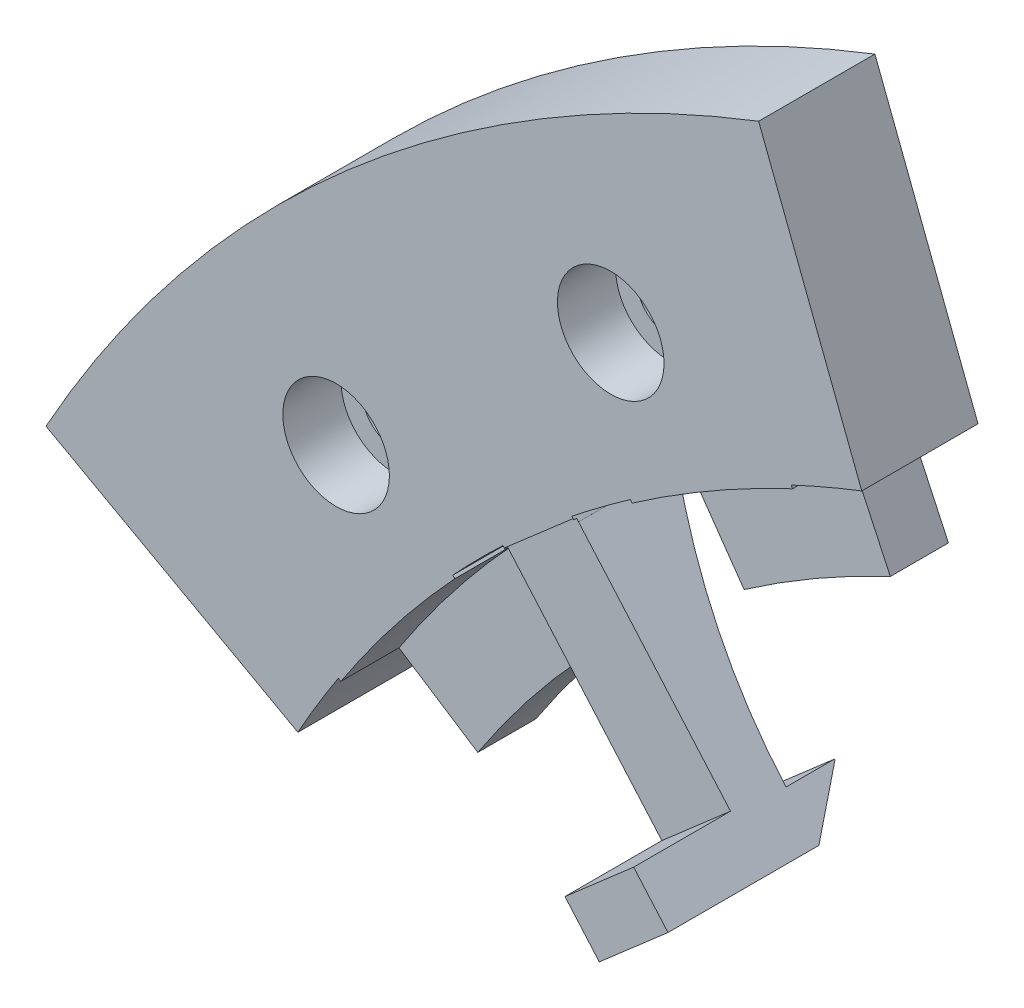
SolidWorks part; units mm, degrees
ref_plane "Front Plane" through (0, 0, 0) normal (1, 0, 0) x (0, 1, 0)
ref_plane "Top Plane" through (0, 0, 0) normal (0, 0, 1) x (0, 1, 0)
ref_plane "Right Plane" through (0, 0, 0) normal (0, 1, 0) x (-1, 0, 0)
sketch "Sketch1" plane through (0, 0, 0) normal (0, 0, 1) x (0, 1, 0)
  line L0 (0, 0) -> (50000, 0) construction
  line L1 (66.793, 25.6394) -> (52.7893, 20.2639)
  line L2 (52.7893, 20.2639) -> (0, 0) construction
  line L3 (34.5874, 62.6291) -> (27.3358, 49.4984)
  line L4 (27.3358, 49.4984) -> (0, 0) construction
  arc A0 (34.5874, 62.6291) -> (66.793, 25.6394) centre (0, 0) cw
  arc A1 (52.7893, 20.2639) -> (27.3358, 49.4984) centre (0, 0) ccw
  dimension "D1" = 71.545
  dimension "D3" = 40.09
  dimension "D4" = 15
  dimension "D2" = 21
extrude "Boss-Extrude1" add sketch "Sketch1" along normal blind 6
ref_axis "Axis1" through (0, 0, 0) along (0, 1, 0)
sketch "Sketch4" plane through (0, 0, 0) normal (0, 0, 1) x (0, 1, 0)
  line L0 (41.3645, 47.5844) -> (0, 0) construction
  line L1 (0, 0) -> (53.4694, 33.4114) construction
  line L2 (0, 0) -> (15.7813, 0) construction
  circle A0 centre (41.3645, 47.5844) radius 1.65
  circle A1 centre (53.4694, 33.4114) radius 1.65
  dimension "D1" = 3.3
  dimension "D2" = 63.05
  dimension "D3" = 32
  dimension "D4" = 49
extrude "Cut-Extrude1" cut sketch "Sketch4" along normal through all
ref_plane "Plane1" through (0, 0, 0) normal (-0.7542, -0.6567, 0) x (0, 0, 1)
ref_axis "Axis2" through (-37.1304, 42.6459, 0) along (0, 0, 1)
sketch "Sketch7" plane through (0, 0, 0) normal (-0.7542, -0.6567, 0) x (0, 0, 1)
  line L0 (6, 56.545) -> (6, 41.545) construction
  line L1 (6, 41.545) -> (3, 41.545)
  line L2 (0.5, 44.045) -> (0.5, 44.295)
  line L3 (0.5, 44.295) -> (3, 44.295)
  line L5 (0, 56.545) -> (6, 56.545) construction
  line L7 (0.5, 44.045) -> (3, 41.545)
  line L8 (6, 41.545) -> (11, 41.545)
  line L9 (11, 41.545) -> (11, 44.545)
  line L10 (11, 44.545) -> (6, 44.545)
  line L11 (6, 44.545) -> (6, 56.545)
  line L12 (0.5, 56.545) -> (6, 56.545)
  arc A1 (3, 44.295) -> (0.5, 56.545) centre (-28.2625, 44.295) ccw
  dimension "D4" = 45
  dimension "D1" = 15
  dimension "D2" = 3
  dimension "D3" = 5
  dimension "D5" = 3
  dimension "D6" = 5.5
  dimension "D7" = 3
  dimension "D8" = 0.25
extrude "Boss-Extrude2" add sketch "Sketch7" along normal blind 2.5 and the other way blind 2.5
fillet "Fillet1" radius 0.1 3 edges at (-29.0864, 33.407, 3) (-29.2505, 33.5956, 6)
sketch "Sketch8" plane through (0, 0, 0) normal (0, 0, 1) x (0, 1, 0)
  line L0 (0, 0) -> (30.7966, 47.4226) construction
  line L1 (38.5636, 41.3544) -> (0, 0) construction
  line L2 (0, 0) -> (46.319, 32.4329) construction
  line L3 (51.2472, 23.8969) -> (0, 0) construction
  line L4 (30.7966, 47.4226) -> (28.0734, 43.2293)
  line L5 (38.5636, 41.3544) -> (35.1536, 37.6976)
  line L6 (46.319, 32.4329) -> (42.2232, 29.565)
  line L7 (51.2472, 23.8969) -> (46.7156, 21.7839)
  line L8 (0, 0) -> (15.7813, 0) construction
  arc A0 (40.9626, 38.9795) -> (27.3358, 49.4984) centre (0, 0) ccw construction
  arc A1 (52.7893, 20.2639) -> (44.2458, 35.2086) centre (0, 0) ccw construction
  arc A2 (30.7966, 47.4226) -> (38.5636, 41.3544) centre (0, 0) cw
  arc A3 (46.319, 32.4329) -> (51.2472, 23.8969) centre (0, 0) cw
  arc A4 (28.0734, 43.2293) -> (35.1536, 37.6976) centre (0, 0) cw
  arc A5 (42.2232, 29.565) -> (46.7156, 21.7839) centre (0, 0) cw
  dimension "D1" = 51.545
  dimension "D2" = 56.545
  dimension "D3" = 25
  dimension "D4" = 10
  dimension "D5" = 12
  dimension "D6" = 10
extrude "Boss-Extrude3" add sketch "Sketch8" along normal blind 3 contours L4 A4 L5 A2 | L5 A4 L4 A2 | L7 A5 L6 A3 region at (-42.5643, 33.2549, 0)
sketch "Sketch9" plane through (0, 0, 6) normal (0, 0, 1) x (1, 0, 0)
  circle A0 centre (-47.5844, 41.3645) radius 2.75
  circle A1 centre (-33.4114, 53.4694) radius 2.75
  dimension "D1" = 5.5
extrude "Cut-Extrude2" cut sketch "Sketch9" against normal blind 3
sketch "Sketch10" plane through (0, 0, 0) normal (0, 0, 1) x (0, 1, 0)
  line L0 (38.5636, 41.3544) -> (35.1536, 37.6976)
  line L1 (30.7966, 47.4226) -> (28.0734, 43.2293)
  line L2 (46.319, 32.4329) -> (42.2232, 29.565)
  line L3 (46.7156, 21.7839) -> (51.2472, 23.8969)
  line L4 (44.2458, 35.2086) -> (32.9746, 25.3951)
  line L5 (40.9164, 38.9393) -> (29.6914, 29.1661)
  arc A0 (28.0734, 43.2293) -> (35.1536, 37.6976) centre (0, 0) cw
  arc A1 (42.2232, 29.565) -> (46.7156, 21.7839) centre (0, 0) cw
  arc A2 (46.7156, 21.7839) -> (42.2232, 29.565) centre (0, 0) ccw construction
extrude "ToleranceCut" cut sketch "Sketch10" along normal through all thin thin type mid plane wall 0.3
sketch "Sketch16" plane through (0, 0, 0) normal (-0.7542, -0.6567, 0) x (0, 0, 1)
  line L0 (6, 56.545) -> (6, 41.545) construction
  line L1 (6, 41.545) -> (3, 41.545)
  line L2 (0.5, 44.045) -> (0.5, 44.295)
  line L3 (0.5, 44.295) -> (3, 44.295)
  line L5 (0, 56.545) -> (6, 56.545) construction
  line L7 (0.5, 44.045) -> (3, 41.545)
  line L8 (6, 41.545) -> (11, 41.545)
  line L9 (11, 41.545) -> (11, 44.545)
  line L10 (11, 44.545) -> (6, 44.545)
  line L11 (6, 44.545) -> (6, 56.545)
  arc A1 (3, 44.295) -> (0.5, 56.545) centre (-28.2625, 44.295) ccw
  point P2 (0, 0)
  point P9 (0, 0)
  point P15 (0, 0)
  point P16 (0, 0)
  dimension "D4" = 45
  dimension "D1" = 15
  dimension "D2" = 3
  dimension "D3" = 5
  dimension "D5" = 3
  dimension "D6" = 5.5
  dimension "D7" = 3
  dimension "D8" = 0.25
  dimension "D9" = 6
extrude "ToleranceCut2" cut sketch "Sketch16" against normal blind 2.35 and the other way blind 2.35 thin contours A1 L3 L2 L7 L1 L8 L9 L10 L11 thin type mid plane wall 0.3
sketch "Sketch17" plane through (0, 0, 0) normal (0, 0, 1) x (0, 1, 0)
  line L0 (28.2808, 43.2732) -> (30.9223, 47.3408) construction
  line L1 (41.0148, 38.8262) -> (41.1028, 38.9027) construction
  line L2 (46.4048, 32.3099) -> (42.4319, 29.528) construction
  line L3 (52.7893, 20.2639) -> (66.793, 25.6394) construction
  line L4 (52.7894, 20.264) -> (66.793, 25.6394)
  line L5 (27.3358, 49.4984) -> (34.5874, 62.6291)
  arc A0 (27.3358, 49.4984) -> (30.9223, 47.3408) centre (0, 0) cw
  arc A1 (38.4538, 41.4566) -> (41.066, 38.8707) centre (0, 0) cw
  arc A2 (44.1473, 35.3217) -> (46.3996, 32.3062) centre (0, 0) cw
  arc A3 (51.1837, 24.0329) -> (52.7894, 20.264) centre (0, 0) cw
extrude "Cut-Extrude-Thin1" cut sketch "Sketch17" along normal blind 10 thin thin type mid plane wall 0.3
